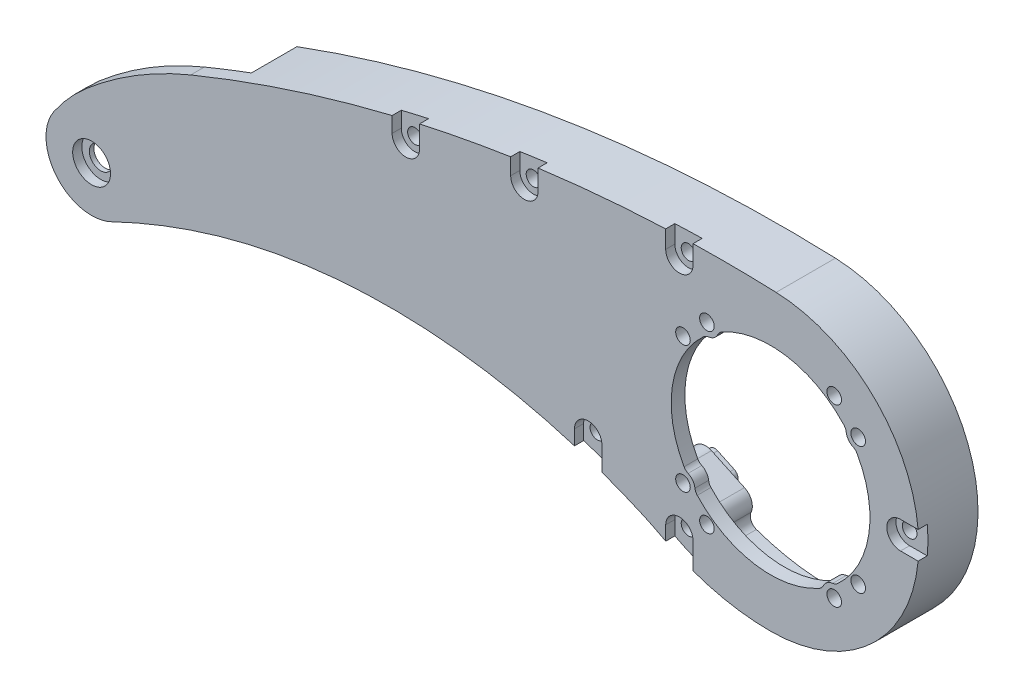
SolidWorks part; units mm, degrees
material "6061-T6 (SS)"
ref_plane "前视基准面" through (0, 0, 0) normal (0, 0, 1) x (1, 0, 0)
ref_plane "上视基准面" through (0, 0, 0) normal (0, 1, 0) x (1, 0, 0)
ref_plane "右视基准面" through (0, 0, 0) normal (1, 0, 0) x (0, 0, -1)
other "Configuration Table"
sketch "草图1" plane through (0, 0, 0) normal (0, 0, 1) x (1, 0, 0)
  line L0 (-74.3846, 0) -> (17.4339, 0) construction
  line L1 (0, 31.8895) -> (0, -25.7876) construction
  line L2 (0, 0) -> (19.2142, 13.9599) construction
  line L3 (0, 0) -> (13.9599, 19.2142) construction
  line L4 (0, 0) -> (-148.9161, -18) construction
  line L6 (0, 0) -> (-1.2281, 22.9672) construction
  line L8 (-1.2281, 22.9672) -> (-150.1441, 4.9672) construction
  line L9 (-150.1441, 4.9672) -> (-148.9161, -18) construction
  line L10 (-148.9161, -18) -> (-97.5528, -158.9319)
  line L12 (0, 0) -> (-103.1063, -167.9797) construction
  arc A116 (16.0762, 14.724) -> (-10.7394, 18.9712) centre (0, 0) ccw
  circle A117 centre (0, 0) radius 23.75 construction
  circle A118 centre (19.2142, 13.9599) radius 1.6
  circle A119 centre (13.9599, 19.2142) radius 1.6
  circle A120 centre (19.2142, -13.9599) radius 1.6
  circle A121 centre (13.9599, -19.2142) radius 1.6
  circle A122 centre (-13.9599, -19.2142) radius 1.6
  circle A123 centre (-19.2142, -13.9599) radius 1.6
  circle A124 centre (-19.2142, 13.9599) radius 1.6
  circle A125 centre (-13.9599, 19.2142) radius 1.6
  arc A126 (0, -32.5) -> (1.2171, 32.4772) centre (0, 0) ccw
  arc A127 (-157.1671, -12.3502) -> (-144.5702, -27.0063) centre (-148.9161, -18) ccw
  arc A134 (-28.3708, -24.2609) -> (-127.3793, -19.9637) centre (-83.3912, -149.2082) ccw
  arc A135 (-127.3793, -19.9637) -> (-144.5702, -27.0063) centre (-78.0965, -164.7651) ccw
  arc A136 (1.2171, 32.4772) -> (-127.1723, 9.5805) centre (-10.2849, -274.4361) ccw
  arc A138 (-23.6381, -26.5665) -> (-28.3708, -24.2609) centre (-55.9067, -86.7929) ccw
  arc A139 (0, -32.5) -> (-23.6381, -26.5665) centre (0, 17.5518) cw
  arc A140 (16.5853, 13.6255) -> (18.0838, 11.5631) centre (19.2142, 13.9599) ccw
  arc A141 (16.5853, 13.6255) -> (16.0762, 14.724) centre (14.6013, 13.3732) ccw
  arc A142 (18.0838, 11.5631) -> (18.9712, 10.7394) centre (17.2307, 9.7541) cw
  arc A143 (11.5631, -18.0838) -> (10.7394, -18.9712) centre (9.7541, -17.2307) cw
  arc A144 (13.6255, -16.5853) -> (11.5631, -18.0838) centre (13.9599, -19.2142) ccw
  arc A145 (13.6255, -16.5853) -> (14.724, -16.0762) centre (13.3732, -14.6013) ccw
  arc A146 (-18.0838, -11.5631) -> (-18.9712, -10.7394) centre (-17.2307, -9.7541) cw
  arc A147 (-16.5853, -13.6255) -> (-18.0838, -11.5631) centre (-19.2142, -13.9599) ccw
  arc A148 (-16.5853, -13.6255) -> (-16.0762, -14.724) centre (-14.6013, -13.3732) ccw
  arc A149 (-11.5631, 18.0838) -> (-10.7394, 18.9712) centre (-9.7541, 17.2307) cw
  arc A150 (-13.6255, 16.5853) -> (-11.5631, 18.0838) centre (-13.9599, 19.2142) ccw
  arc A151 (-13.6255, 16.5853) -> (-14.724, 16.0762) centre (-13.3732, 14.6013) ccw
  arc A152 (-16.0762, -14.724) -> (10.7394, -18.9712) centre (0, 0) ccw
  arc A153 (14.724, -16.0762) -> (18.9712, 10.7394) centre (0, 0) ccw
  arc A154 (-14.724, 16.0762) -> (-18.9712, -10.7394) centre (0, 0) ccw
  arc A155 (-127.1723, 9.5805) -> (-150.1438, -4.5112) centre (-94.9478, -68.7195) ccw
  arc A156 (-150.1438, -4.5112) -> (-157.1671, -12.3502) centre (-123.7132, -35.2574) ccw
  point P27 (0, 0)
  point P73 (0, 0)
  dimension "D1" = 43.6
  dimension "D3" = 36
  dimension "D4" = 3.2
  dimension "D2" = 47.5
  dimension "D6" = 3.2
  dimension "D8" = 65
  dimension "D15" = 20
  dimension "D16" = 5.3
  dimension "D17" = 2
  dimension "D5" = 18
  dimension "D9" = 18
  dimension "D10" = 150
  dimension "D11" = 23
  dimension "D12" = 150
  dimension "D13" = 103.132
  dimension "D14" = 51.566
  dimension "D7" = 4
  dimension "D18" = 4
extrude "凸台-拉伸1" add sketch "草图1" along normal blind 3 contours A135 A134 A138 A126 A127 A125 A124 A123 A122 A121 A120 A119 A118 A116 region at (-60.0169, 1.611, 0)
sketch "草图2" plane through (0, 0, 0) normal (0, 0, -1) x (-1, 0, 0)
  line L0 (-28.5, 0) -> (0, 0) construction
  line L2 (0, 0) -> (18.5599, 13.5842) construction
  line L3 (18.5599, 13.5842) -> (167.476, -4.4158) construction
  line L4 (167.476, -4.4158) -> (148.9161, -18) construction
  line L5 (148.9161, -18) -> (10.6983, -76.2738) construction
  line L7 (25.351, 15.2815) -> (162.3611, -1.2794) construction
  line L9 (24.751, 10.3176) -> (161.7611, -6.2433) construction
  line L11 (19.8643, 25.54) -> (27.8561, 25.1781)
  line L13 (18.7235, -21.0787) -> (25.9631, -17.6745)
  line L16 (53.5282, 22.5613) -> (61.4287, 21.3032)
  line L17 (79.2716, 17.6568) -> (87.0322, 15.7143)
  line L19 (116.7753, -9.6208) -> (124.5035, -11.6883)
  line L20 (39.1553, -12.6715) -> (46.8316, -10.4188)
  arc A111 (-1.1422, 30.4786) -> (-30.0624, 5.1483) centre (0, 0) ccw
  arc A112 (0, -30.5) -> (16.1065, -27.7202) centre (0, 17.5518) ccw
  arc A114 (110.6875, -13.3991) -> (53.0075, -14.0564) centre (83.3912, -149.2082) ccw
  arc A115 (128.6525, -18.2859) -> (127.8763, -18.0203) centre (78.0965, -164.7651) ccw
  arc A116 (144.5702, -27.0063) -> (157.1671, -12.3502) centre (148.9161, -18) ccw
  arc A118 (157.1671, -12.3502) -> (150.1438, -4.5112) centre (123.7132, -35.2574) ccw
  arc A119 (127.1723, 9.5805) -> (-1.2171, 32.4772) centre (10.2849, -274.4361) ccw
  arc A120 (-1.2171, 32.4772) -> (0, -32.5) centre (0, 0) ccw
  arc A121 (-1.0673, 28.48) -> (0, -28.5) centre (0, 0) ccw construction
  arc A122 (0, -32.5) -> (23.6381, -26.5665) centre (0, 17.5518) ccw
  arc A123 (28.3708, -24.2609) -> (23.6381, -26.5665) centre (55.9067, -86.7929) ccw
  arc A124 (127.3793, -19.9637) -> (28.3708, -24.2609) centre (83.3912, -149.2082) ccw
  arc A125 (144.5702, -27.0063) -> (127.3793, -19.9637) centre (78.0965, -164.7651) ccw
  arc A126 (144.5702, -27.0063) -> (157.1671, -12.3502) centre (148.9161, -18) ccw
  arc A128 (127.1723, 9.5805) -> (-1.2171, 32.4772) centre (10.2849, -274.4361) ccw
  arc A129 (-1.2171, 32.4772) -> (0, -32.5) centre (0, 0) ccw
  arc A130 (0, -32.5) -> (23.6381, -26.5665) centre (0, 17.5518) ccw
  arc A131 (28.3708, -24.2609) -> (23.6381, -26.5665) centre (55.9067, -86.7929) ccw
  arc A132 (127.3793, -19.9637) -> (28.3708, -24.2609) centre (83.3912, -149.2082) ccw
  arc A133 (144.5702, -27.0063) -> (127.3793, -19.9637) centre (78.0965, -164.7651) ccw
  arc A134 (0, -28.5) -> (21.749, -23.0407) centre (0, 17.5518) ccw construction
  arc A135 (26.7587, -20.6001) -> (21.749, -23.0407) centre (55.9067, -86.7929) ccw construction
  arc A136 (128.6681, -16.177) -> (26.7587, -20.6001) centre (83.3912, -149.2082) ccw construction
  arc A137 (146.3086, -23.4038) -> (128.6681, -16.177) centre (78.0965, -164.7651) ccw construction
  arc A138 (146.3086, -23.4038) -> (153.7238, -14.4104) centre (148.9161, -18) ccw construction
  arc A139 (153.7238, -14.4104) -> (126.0955, 5.6977) centre (120.8678, -30.5198) ccw construction
  arc A140 (126.0955, 5.6977) -> (-1.0673, 28.48) centre (10.2849, -274.4361) ccw construction
  arc A141 (-28.3421, -2.9958) -> (-28.3421, 2.9958) centre (-28.5, 0) ccw
  arc A142 (-28.3421, 2.9958) -> (-30.0624, 5.1483) centre (-28.2451, 4.837) cw
  arc A143 (-28.3421, -2.9958) -> (-30.0624, -5.1483) centre (-28.2451, -4.837) ccw
  arc A144 (-30.0624, -5.1483) -> (0, -30.5) centre (0, 0) ccw
  circle A145 centre (-28.5, 0) radius 1.6
  arc A146 (-1.1422, 30.4786) -> (0, -30.5) centre (0, 0) ccw construction
  circle A147 centre (18.5599, 13.5842) radius 7 construction
  circle A148 centre (167.476, -4.4158) radius 6 construction
  arc A149 (17.0011, 28.6182) -> (19.8643, 25.54) centre (20, 28.5369) ccw
  arc A150 (27.8561, 25.1781) -> (30.9858, 27.985) centre (27.9918, 28.175) ccw
  arc A151 (17.0011, 28.6182) -> (15.0491, 30.6555) centre (15.0181, 28.672) ccw
  arc A152 (30.9858, 27.985) -> (33.1139, 29.8374) centre (32.9655, 27.8593) cw
  arc A153 (15.0491, 30.6555) -> (-1.1422, 30.4786) centre (10.2849, -274.4361) ccw
  circle A154 centre (20, 28.5369) radius 1.6
  arc A155 (126.6313, 7.6402) -> (-1.1422, 30.4786) centre (10.2849, -274.4361) ccw construction
  arc A156 (17.2617, -25.019) -> (18.7235, -21.0787) centre (20, -23.7935) cw
  arc A157 (25.9631, -17.6745) -> (30.0023, -19.2201) centre (27.2396, -20.3894) cw
  circle A158 centre (20, -23.7935) radius 1.6
  arc A159 (17.2617, -25.019) -> (16.1065, -27.7202) centre (15.4362, -25.8359) cw
  arc A160 (30.0023, -19.2201) -> (32.6241, -20.3211) centre (31.8778, -18.4263) ccw
  circle A161 centre (54, 25.524) radius 1.6
  arc A162 (27.5648, -22.4305) -> (22.6935, -24.8036) centre (55.9067, -86.7929) ccw construction
  arc A163 (0, -30.5) -> (22.6935, -24.8036) centre (0, 17.5518) ccw construction
  arc A164 (128.0237, -18.0703) -> (27.5648, -22.4305) centre (83.3912, -149.2082) ccw construction
  arc A165 (51.0293, 25.9419) -> (53.5282, 22.5613) centre (54, 25.524) ccw
  arc A166 (61.4287, 21.3032) -> (64.8541, 23.7404) centre (61.9005, 24.2659) ccw
  arc A167 (51.0293, 25.9419) -> (49.3187, 28.1856) centre (49.0649, 26.2183) ccw
  arc A168 (64.8541, 23.7404) -> (67.177, 25.3419) centre (66.8071, 23.393) cw
  arc A169 (49.3187, 28.1856) -> (33.1139, 29.8374) centre (10.2849, -274.4361) ccw
  circle A170 centre (80, 20.567) radius 1.6
  arc A171 (77.077, 21.2425) -> (79.2716, 17.6568) centre (80, 20.567) ccw
  arc A172 (87.0322, 15.7143) -> (90.6571, 17.8435) centre (87.7606, 18.6246) ccw
  arc A173 (77.077, 21.2425) -> (75.5687, 23.6269) centre (75.1443, 21.6892) ccw
  arc A175 (75.5687, 23.6269) -> (67.177, 25.3419) centre (10.2849, -274.4361) ccw
  circle A176 centre (40, -15.5501) radius 1.6
  circle A177 centre (116, -12.5189) radius 1.6
  arc A178 (37.1566, -16.5068) -> (39.1553, -12.6715) centre (40, -15.5501) cw
  arc A180 (37.1566, -16.5068) -> (35.9243, -19.0695) centre (35.2265, -17.1563) cw
  arc A182 (35.9243, -19.0695) -> (32.6241, -20.3211) centre (83.3912, -149.2082) ccw
  arc A183 (113.0746, -11.854) -> (116.7753, -9.6208) centre (116, -12.5189) cw
  arc A184 (124.5035, -11.6883) -> (126.5902, -15.4859) centre (123.7282, -14.5864) cw
  arc A185 (113.0746, -11.854) -> (110.6875, -13.3991) centre (111.0888, -11.4026) cw
  arc A186 (126.5902, -15.4859) -> (127.8763, -18.0203) centre (128.5292, -16.0954) ccw
  arc A187 (128.6525, -18.2859) -> (129.8863, -20.8413) centre (128, -20.1764) cw
  arc A188 (145.4394, -25.205) -> (128.0237, -18.0703) centre (78.0965, -164.7651) ccw construction
  arc A189 (144.5702, -27.0063) -> (127.3793, -19.9637) centre (78.0965, -164.7651) ccw construction
  arc A190 (145.4394, -25.205) -> (155.4422, -13.3729) centre (148.9161, -18) ccw construction
  arc A191 (75.5687, 23.6269) -> (93.1109, 19.2362) centre (10.2849, -274.4361) cw construction
  arc A192 (90.6571, 17.8435) -> (93.1109, 19.2362) centre (92.5724, 17.327) cw
  arc A193 (155.4422, -13.3729) -> (126.6313, 7.6402) centre (120.8678, -30.5198) ccw construction
  arc A194 (15.0491, 30.6555) -> (33.1139, 29.8374) centre (10.2849, -274.4361) cw construction
  arc A195 (49.3187, 28.1856) -> (67.177, 25.3419) centre (10.2849, -274.4361) cw construction
  arc A196 (93.1109, 19.2362) -> (114.3181, 12.4099) centre (10.2849, -274.4361) cw
  arc A197 (114.3181, 12.4099) -> (116.8779, 13.6021) centre (115, 14.2901) ccw
  arc A198 (46.8316, -10.4188) -> (50.5858, -12.566) centre (47.6763, -13.2974) cw
  arc A199 (50.5858, -12.566) -> (53.0075, -14.0564) centre (52.5608, -12.0695) ccw
  arc A200 (54.5841, -13.7116) -> (56.9593, -15.2663) centre (55, -15.6678) cw
  arc A207 (157.1671, -12.3502) -> (127.1723, 9.5805) centre (120.8678, -30.5198) ccw construction
  arc A208 (157.1671, -12.3502) -> (150.1438, -4.5112) centre (123.7132, -35.2574) ccw
  arc A209 (150.1438, -4.5112) -> (127.1723, 9.5805) centre (94.9478, -68.7195) ccw
  arc A210 (150.1438, -4.5112) -> (127.1723, 9.5805) centre (94.9478, -68.7195) ccw
  point P113 (16.5105, -418.9921)
  arc M20 (127.1723, 9.5805) -> (-1.2171, 32.4772) centre (10.2849, -274.4361) ccw
  arc M21 (-1.2171, 32.4772) -> (0, -32.5) centre (0, 0) ccw
  arc M22 (0, -32.5) -> (23.6381, -26.5665) centre (0, 17.5518) ccw
  arc M23 (23.6381, -26.5665) -> (28.3708, -24.2609) centre (55.9067, -86.7929) cw
  arc M24 (28.3708, -24.2609) -> (127.3793, -19.9637) centre (83.3912, -149.2082) cw
  arc M25 (127.3793, -19.9637) -> (144.5702, -27.0063) centre (78.0965, -164.7651) cw
  dimension "D7" = 150
  dimension "D9" = 14
  dimension "D11" = 12
  dimension "D12" = 150
  dimension "D13" = 8
  dimension "D10" = 2.5
  dimension "D8" = 166.66
  dimension "D14" = 20
  dimension "D15" = 8
  dimension "D16" = 8
  dimension "D17" = 8
  dimension "D18" = 54
  dimension "D19" = 80
  dimension "D20" = 8
  dimension "D21" = 40
  dimension "D22" = 116
  dimension "D23" = 8
  dimension "D6" = 23
  dimension "D25" = 128
  dimension "D26" = 2
  dimension "D27" = 115
  dimension "D28" = 20
  dimension "D4" = 6
  dimension "D5" = 3.2
  dimension "D24" = 2
  dimension "D29" = 2
  dimension "D1" = 0
  dimension "D2" = 2
  dimension "D3" = 2
  dimension "D30" = 55
extrude "凸台-拉伸2" add sketch "草图2" along normal blind 10 contours M20 M21 M22 M23 M24 M25 region at (-17.9227, 26.6047, 0)
sketch "草图4" plane through (0, 0, -10) normal (0, 0, -1) x (-1, 0, 0)
  line L0 (20, 28.5369) -> (27.9918, 28.175) construction
  line L3 (61.9005, 24.2659) -> (54, 25.524) construction
  line L8 (80, 20.567) -> (87.7606, 18.6246) construction
  line L9 (20, -23.7935) -> (27.2396, -20.3894) construction
  line L10 (40, -15.5501) -> (47.6763, -13.2974) construction
  line L11 (116, -12.5189) -> (123.7282, -14.5864) construction
  line L12 (27.2396, -20.3894) -> (23.6198, -22.0915) construction
  line L15 (27.8779, -21.7468) -> (24.2581, -23.4489)
  line L24 (26.6013, -19.032) -> (22.9815, -20.734)
  line L27 (27.9918, 28.175) -> (23.9959, 28.356) construction
  line L30 (27.924, 26.6766) -> (23.9281, 26.8575)
  line L33 (28.0597, 29.6735) -> (24.0638, 29.8545)
  line L36 (61.9005, 24.2659) -> (57.9502, 24.8949) construction
  line L39 (87.7606, 18.6246) -> (83.8803, 19.5958) construction
  line L40 (87.3964, 17.1695) -> (83.5161, 18.1407)
  line L41 (88.1248, 20.0797) -> (84.2445, 21.0509)
  line L42 (123.7282, -14.5864) -> (119.8641, -13.5526) construction
  line L43 (123.3406, -16.0354) -> (119.4765, -15.0017)
  line L44 (124.1159, -13.1373) -> (120.2518, -12.1036)
  line L45 (47.6763, -13.2974) -> (43.8382, -14.4238) construction
  line L46 (48.0987, -14.7367) -> (44.2605, -15.8631)
  line L47 (47.2539, -11.8581) -> (43.4158, -12.9845)
  line L48 (61.6646, 22.7845) -> (57.7143, 23.4136)
  line L49 (62.1363, 25.7472) -> (58.1861, 26.3763)
  arc A24 (27.8779, -21.7468) -> (26.6013, -19.032) centre (27.2396, -20.3894) ccw
  arc A25 (22.9815, -20.734) -> (24.2581, -23.4489) centre (23.6198, -22.0915) ccw
  arc A26 (27.924, 26.6766) -> (28.0597, 29.6735) centre (27.9918, 28.175) ccw
  arc A27 (24.0638, 29.8545) -> (23.9281, 26.8575) centre (23.9959, 28.356) ccw
  arc A30 (87.3964, 17.1695) -> (88.1248, 20.0797) centre (87.7606, 18.6246) ccw
  arc A31 (84.2445, 21.0509) -> (83.5161, 18.1407) centre (83.8803, 19.5958) ccw
  arc A32 (123.3406, -16.0354) -> (124.1159, -13.1373) centre (123.7282, -14.5864) ccw
  arc A33 (120.2518, -12.1036) -> (119.4765, -15.0017) centre (119.8641, -13.5526) ccw
  arc A34 (48.0987, -14.7367) -> (47.2539, -11.8581) centre (47.6763, -13.2974) ccw
  arc A35 (43.4158, -12.9845) -> (44.2605, -15.8631) centre (43.8382, -14.4238) ccw
  arc A36 (61.6646, 22.7845) -> (62.1363, 25.7472) centre (61.9005, 24.2659) ccw
  arc A37 (58.1861, 26.3763) -> (57.7143, 23.4136) centre (57.9502, 24.8949) ccw
  point P12 (25.4297, -21.2404)
  point P18 (25.9939, 28.2655)
  point P24 (59.9253, 24.5804)
  point P30 (85.8204, 19.1102)
  point P36 (121.7962, -14.0695)
  point P42 (45.7572, -13.8606)
  dimension "D2" = 1.5
  dimension "D1" = 4
extrude "凸台-拉伸3" add sketch "草图4" along normal blind 2 contours L33 A27 L30 A26 | L49 A37 L48 A36 | A30 L41 A31 L40 | A34 L47 A35 L46 | A24 L24 A25 L15
sketch "草图5" plane through (0, 0, -10) normal (0, 0, -1) x (-1, 0, 0)
  circle A2 centre (-28.5, 0) radius 1.6 construction
  circle A4 centre (-28.5, 0) radius 1.6
  circle A6 centre (54, 25.524) radius 1.6 construction
  circle A8 centre (80, 20.567) radius 1.6 construction
  circle A12 centre (40, -15.5501) radius 1.6 construction
  circle A14 centre (20, -23.7935) radius 1.6 construction
  circle A27 centre (20, 28.5369) radius 1.6 construction
  circle A28 centre (54, 25.524) radius 1.6
  circle A29 centre (80, 20.567) radius 1.6
  circle A31 centre (40, -15.5501) radius 1.6
  circle A32 centre (20, -23.7935) radius 1.6
  circle A33 centre (20, 28.5369) radius 1.6
extrude "切除-拉伸1" cut sketch "草图5" against normal up to next
sketch "草图10" plane through (0, 0, 0) normal (0, 0, -1) x (-1, 0, 0)
  circle A0 centre (148.9161, -18) radius 2.5
  dimension "D1" = 5
extrude "切除-拉伸4" cut sketch "草图10" against normal up to next
sketch "草图11" plane through (0, 0, 3) normal (0, 0, 1) x (1, 0, 0)
  circle A0 centre (-148.9161, -18) radius 4.15
  dimension "D1" = 8.3
extrude "切除-拉伸5" cut sketch "草图11" against normal blind 2
sketch "草图13" plane through (0, 0, 3) normal (0, 0, 1) x (1, 0, 0)
  line L0 (-83, 20.567) -> (-83, 23.9606)
  line L1 (-77, 20.567) -> (-77, 25.3591)
  line L2 (-57, 25.524) -> (-57, 29.1191)
  line L3 (-51, 25.524) -> (-51, 29.982)
  line L4 (-23, 28.5369) -> (-23, 32.4293)
  line L5 (-17, 28.5369) -> (-17, 32.6192)
  line L8 (-43, -15.5501) -> (-43, -18.7949)
  line L9 (-37, -15.5501) -> (-37, -20.8067)
  line L10 (-23, -23.7935) -> (-23, -26.9025)
  line L11 (-17, -23.7935) -> (-17, -29.5246)
  line L12 (28.5, 3) -> (32.3612, 3)
  line L13 (28.5, -3) -> (32.3612, -3)
  line L14 (28.5, 3) -> (28.5, -3) construction
  arc A0 (-83, 20.567) -> (-77, 20.567) centre (-80, 20.567) ccw
  arc A1 (-57, 25.524) -> (-51, 25.524) centre (-54, 25.524) ccw
  arc A2 (-23, 28.5369) -> (-17, 28.5369) centre (-20, 28.5369) ccw
  arc A3 (28.5, 3) -> (28.5, -3) centre (28.5, 0) ccw
  arc A5 (-37, -15.5501) -> (-43, -15.5501) centre (-40, -15.5501) ccw
  arc A7 (-23.6381, -26.5665) -> (0, -32.5) centre (0, 17.5518) ccw construction
  arc A8 (1.2171, 32.4772) -> (-127.1723, 9.5805) centre (-10.2849, -274.4361) ccw construction
  arc A9 (-28.3708, -24.2609) -> (-127.3793, -19.9637) centre (-83.3912, -149.2082) ccw construction
  arc A10 (-23.6381, -26.5665) -> (0, -32.5) centre (0, 17.5518) ccw
  arc A11 (-23.6381, -26.5665) -> (-28.3708, -24.2609) centre (-55.9067, -86.7929) ccw construction
  arc A12 (0, -32.5) -> (1.2171, 32.4772) centre (0, 0) ccw construction
  arc A13 (1.2171, 32.4772) -> (-127.1723, 9.5805) centre (-10.2849, -274.4361) ccw
  arc A15 (0, -32.5) -> (1.2171, 32.4772) centre (0, 0) ccw
  arc A16 (-23.6381, -26.5665) -> (-28.3708, -24.2609) centre (-55.9067, -86.7929) ccw
  arc A18 (-17, -23.7935) -> (-23, -23.7935) centre (-20, -23.7935) ccw
  arc A19 (-28.3708, -24.2609) -> (-127.3793, -19.9637) centre (-83.3912, -149.2082) ccw
  circle M9 centre (28.5, 0) radius 1.6
  circle M10 centre (-54, 25.524) radius 1.6
  circle M11 centre (-80, 20.567) radius 1.6
  circle M13 centre (-40, -15.5501) radius 1.6
  circle M14 centre (-20, -23.7935) radius 1.6
  circle M15 centre (-20, 28.5369) radius 1.6
  arc M17 (-127.3793, -19.9637) -> (-28.3708, -24.2609) centre (-83.3912, -149.2082) cw
  arc M19 (-23.6381, -26.5665) -> (0, -32.5) centre (0, 17.5518) ccw
  arc M20 (0, -32.5) -> (1.2171, 32.4772) centre (0, 0) ccw
  arc M21 (1.2171, 32.4772) -> (-127.1723, 9.5805) centre (-10.2849, -274.4361) ccw
  dimension "D1" = 6
  dimension "D2" = 6
  dimension "D3" = 3
extrude "切除-拉伸6" cut sketch "草图13" against normal blind 2 contours L9 A5 L8 M17 M13 | L11 A18 L10 M19 M14 | L12 L14 L13 M9 M20 | L14 A3 M9 | L4 A2 L5 M21 M15 | L2 A1 L3 M21 M10 | L0 A0 L1 M21 M11 region at (-39.9559, -19.6692, 3) region at (-20.0005, -28.2147, 3) region at (30.7421, 0, 3) region at (-19.9975, 32.4462, 3) region at (-53.9885, 29.4706, 3) region at (-82.9017, 22.2638, 3) region at (28.4329, 2.3, 3)
sketch "草图14" plane through (0, 0, 0) normal (0, 0, -1) x (-1, 0, 0)
  circle A0 centre (148.9161, -18) radius 10
  circle A1 centre (148.9161, -18) radius 7
  dimension "D1" = 14
  dimension "D2" = 20
extrude "凸台-拉伸4" add sketch "草图14" along normal blind 1.5
